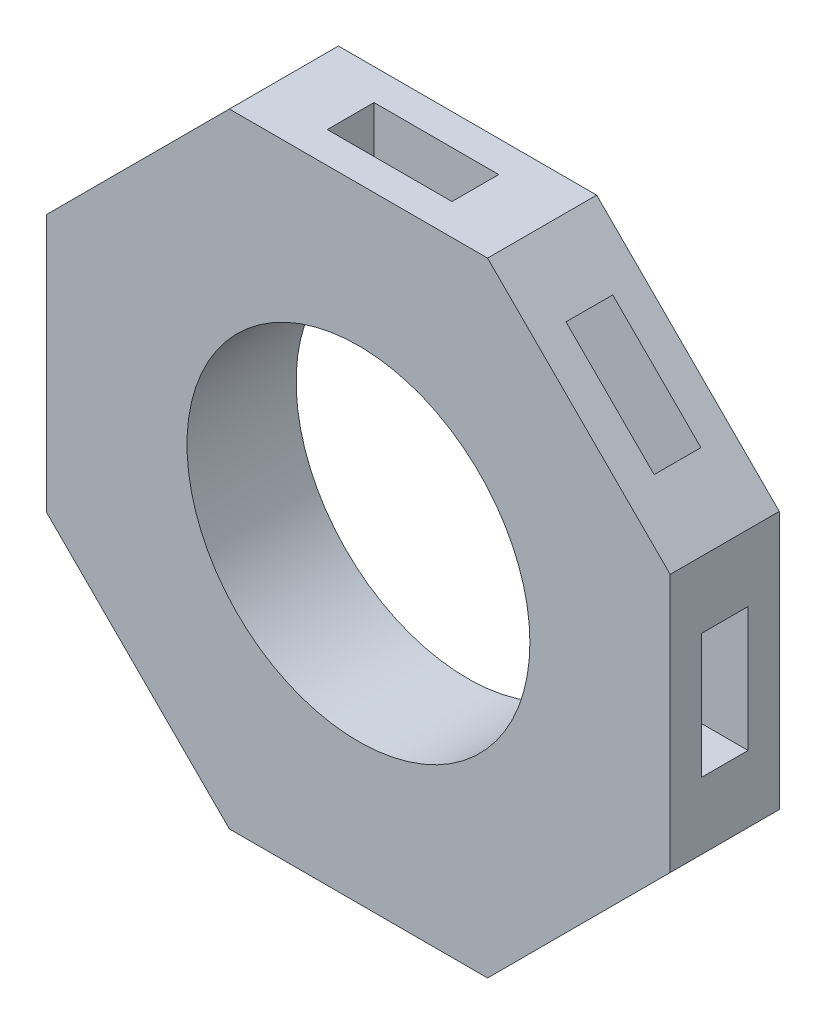
SolidWorks part; units mm, degrees
note: '?' marks a value the reader was unsure of.
ref_plane "Top Plane" through (0, 0, 0) normal (0, 0, 1) x (1, 0, 0)
ref_plane "Right Plane" through (0, 0, 0) normal (0, 1, 0) x (1, 0, 0)
ref_plane "Front Plane" through (0, 0, 0) normal (1, 0, 0) x (0, 0, -1)
ref_axis "x-axis" through (-88.99, 0, 0) along (1, 0, 0)?
ref_axis "y-axis" through (0, -55, 0) along (0, 1, 0)?
ref_axis "z-axis" through (0, 0, 55) along (0, 0, -1)?
sketch "Sketch1" plane through (0, 0, 0) normal (0, 0, 1) x (1, 0, 0)
  line L0 (8.2843, 20) -> (-8.2843, 20)
  line L1 (-20, 8.2843) -> (-20, -8.2843)
  line L2 (-20, -8.2843) -> (-8.2843, -20)
  line L3 (-8.2843, -20) -> (8.2843, -20)
  line L4 (8.2843, -20) -> (20, -8.2843)
  line L5 (20, -8.2843) -> (20, 8.2843)
  line L6 (20, 8.2843) -> (8.2843, 20)
  line L7 (-8.2843, 20) -> (-20, 8.2843)
  line L8 (-20, 0) -> (0, 0) construction
  circle A0 centre (0, 0) radius 11
  circle A1 centre (0, 0) radius 20 construction
  point P15 (11, 0)
  point P16 (-0.2636, -0.4614)
  point P17 (11, 0)
  dimension "D1" = 22
  dimension "D2" = 9
extrude "Boss-Extrude1" add sketch "Sketch1" along normal mid plane 7
sketch "Sketch2" plane through (0, -20, 0) normal (0, -1, 0) x (-1, 0, 0)
  line L0 (-8.2843, 3.5) -> (8.2843, -3.5) construction
  line L1 (-4, -1.5) -> (4, -1.5)
  line L2 (-4, -1.5) -> (-4, 1.5)
  line L3 (-4, 1.5) -> (4, 1.5)
  line L4 (4, -1.5) -> (4, 1.5)
  line L5 (-4, -1.5) -> (4, 1.5) construction
  line L6 (-4, 1.5) -> (4, -1.5) construction
  line L7 (-8.2843, -3.5) -> (8.2843, 3.5) construction
  point P13 (0, 0)
  point P14 (0, 0)
  point P15 (0, 0)
  point P16 (1.5, 4)
  dimension "D2" = 8
  dimension "D3" = 3
extrude "Cut-Extrude3" cut sketch "Sketch2" against normal offset from surface (7.6307 mm away) 2
pattern_circular "CirPattern1" count 8 over 360 about axis through (0, 0, 0) along (0, 0, 1) of "Cut-Extrude3"
